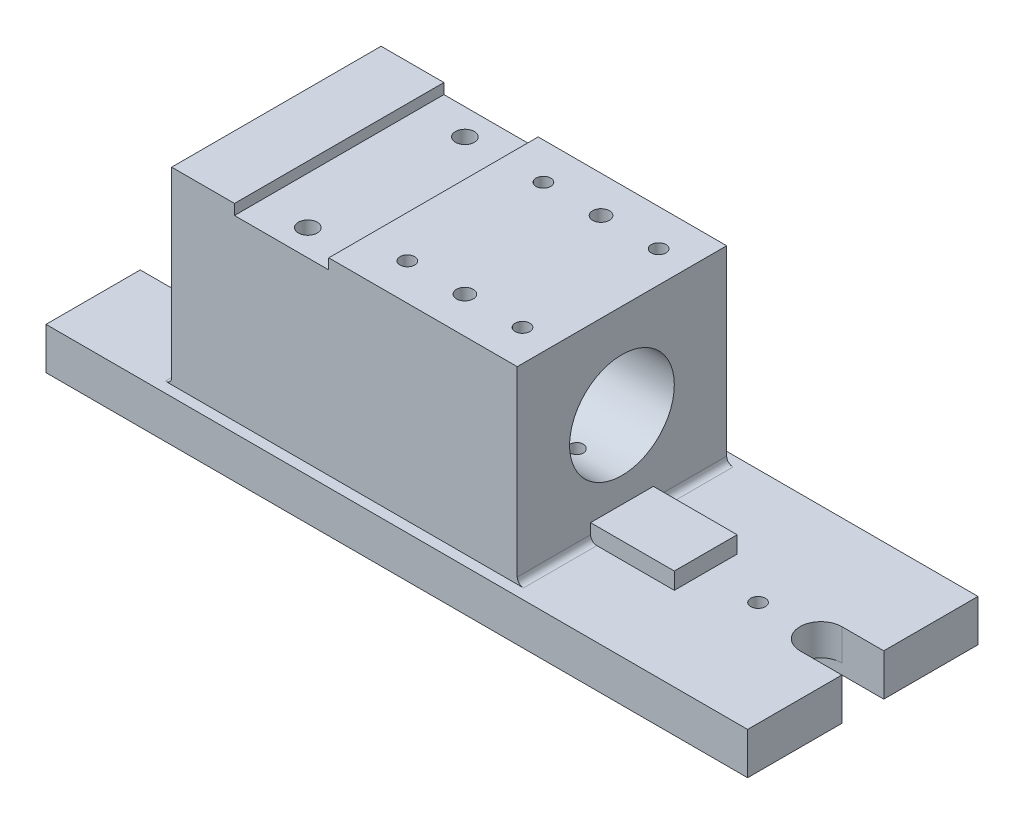
SolidWorks part; units mm, degrees
ref_plane "Спереди" through (0, 0, 0) normal (0, 0, 1) x (1, 0, 0)
ref_plane "Сверху" through (0, 0, 0) normal (0, 1, 0) x (1, 0, 0)
ref_plane "Справа" through (0, 0, 0) normal (1, 0, 0) x (0, 0, -1)
sketch "Эскиз1" plane through (0, 0, 0) normal (0, 1, 0) x (1, 0, 0)
  line L0 (-1085.7045, 0) -> (53199.5194, 0) construction
  line L1 (0, -1085.7045) -> (0, 53199.5194) construction
  line L2 (-147.5, 10) -> (-167.5, 10)
  line L3 (-167.5, -55) -> (167.5, -55)
  line L4 (-167.5, -55) -> (-167.5, -10)
  line L5 (-167.5, 55) -> (167.5, 55)
  line L6 (167.5, -55) -> (167.5, -10)
  line L7 (-167.5, -55) -> (167.5, 55) construction
  line L8 (-167.5, 55) -> (167.5, -55) construction
  line L9 (-147.5, -10) -> (-167.5, -10)
  line L10 (147.5, 10) -> (167.5, 10)
  line L11 (147.5, -10) -> (167.5, -10)
  line L12 (167.5, 10) -> (167.5, 55)
  line L13 (-167.5, 10) -> (-167.5, 55)
  arc A0 (-147.5, -10) -> (-147.5, 10) centre (-147.5, 0) ccw
  arc A1 (147.5, 10) -> (147.5, -10) centre (147.5, 0) ccw
  point P4 (0, 0)
  dimension "D3" = 20
  dimension "D1" = 335
  dimension "D2" = 110
  dimension "D4" = 20
  dimension "D5" = 20
extrude "Бобышка-Вытянуть1" add sketch "Эскиз1" along normal blind 20
sketch "Эскиз2" plane through (0, 0, 0) normal (0, -1, 0) x (1, 0, 0)
  line L0 (-1000, 0) -> (49000, 0) construction
  line L1 (167.5, 55) -> (167.5, 10) construction
  line L2 (40.5, -35) -> (-95.5, -35)
  line L3 (42.5, -33) -> (42.5, 33)
  line L4 (40.5, 35) -> (-95.5, 35)
  line L5 (-97.5, -33) -> (-97.5, 33)
  line L6 (42.5, -35) -> (-97.5, 35) construction
  line L7 (42.5, 35) -> (-97.5, -35) construction
  arc A0 (-95.5, -35) -> (-97.5, -33) centre (-95.5, -33) cw
  arc A1 (40.5, -35) -> (42.5, -33) centre (40.5, -33) ccw
  arc A2 (42.5, 33) -> (40.5, 35) centre (40.5, 33) ccw
  arc A3 (-95.5, 35) -> (-97.5, 33) centre (-95.5, 33) ccw
  point P1 (-27.5, 0)
  dimension "D4" = 2
  dimension "D1" = 70
  dimension "D2" = 125
  dimension "D3" = 265
extrude "Вырез-Вытянуть1" cut sketch "Эскиз2" against normal blind 16
sketch "Эскиз3" plane through (-167.5, 0, 0) normal (-1, 0, 0) x (0, 0, 1)
  line L0 (-10, 20) -> (-10, 0) construction
  line L1 (-10, 5) -> (10, 5)
  line L2 (-10, 5) -> (-10, 0)
  line L3 (-10, 0) -> (10, 0)
  line L4 (10, 5) -> (10, 0)
  line L5 (10, 20) -> (10, 0) construction
  line L6 (-55, 0) -> (-10, 0) construction
  dimension "D1" = 5
extrude "Вырез-Вытянуть2" cut sketch "Эскиз3" against normal through all
sketch "Эскиз4" plane through (0, 20, 0) normal (0, 1, 0) x (1, 0, 0)
  line L0 (-1000, 0) -> (49000, 0) construction
  line L1 (167.5, 10) -> (167.5, 55) construction
  line L2 (-112.5, -50) -> (52.5, -50)
  line L3 (-112.5, -50) -> (-112.5, 50)
  line L4 (-112.5, 50) -> (52.5, 50)
  line L5 (52.5, -50) -> (52.5, 50)
  line L6 (-112.5, -50) -> (52.5, 50) construction
  line L7 (-112.5, 50) -> (52.5, -50) construction
  point P1 (-30, 0)
  dimension "D1" = 100
  dimension "D2" = 115
  dimension "D3" = 280
extrude "Бобышка-Вытянуть2" add sketch "Эскиз4" along normal blind 90
sketch "Эскиз5" plane through (0, 0, 50) normal (0, 0, 1) x (1, 0, 0)
  line L0 (-112.5, 110) -> (52.5, 110) construction
  line L1 (-82.5, 110) -> (-37.5, 110)
  line L2 (-82.5, 110) -> (-82.5, 105)
  line L3 (-82.5, 105) -> (-37.5, 105)
  line L4 (-37.5, 110) -> (-37.5, 105)
  line L5 (167.5, 20) -> (167.5, 0) construction
  dimension "D1" = 5
  dimension "D2" = 205
  dimension "D3" = 250
extrude "Вырез-Вытянуть3" cut sketch "Эскиз5" against normal up to next
sketch "Эскиз6" plane through (0, 20, 0) normal (0, 1, 0) x (1, 0, 0)
  line L0 (-1000, 0) -> (49000, 0) construction
  line L1 (52.5, -50) -> (52.5, 50) construction
  line L2 (92.5, -15) -> (52.5, -15)
  line L3 (92.5, -15) -> (92.5, 15)
  line L4 (92.5, 15) -> (52.5, 15)
  line L5 (52.5, -15) -> (52.5, 15)
  line L6 (92.5, -15) -> (52.5, 15) construction
  line L7 (92.5, 15) -> (52.5, -15) construction
  line L8 (167.5, 10) -> (167.5, 55) construction
  point P1 (72.5, 0)
  dimension "D1" = 30
  dimension "D2" = 75
extrude "Бобышка-Вытянуть3" add sketch "Эскиз6" along normal blind 8
sketch "Эскиз7" plane through (-167.5, 0, 0) normal (-1, 0, 0) x (0, 0, 1)
  line L1 (0, 0) -> (91.7061, 0)
  line L2 (0, 0) -> (0, 136.0495)
  line L3 (0, 136.0495) -> (91.7061, 136.0495)
  line L4 (91.7061, 0) -> (91.7061, 136.0495)
  dimension "D1" = 91.7061
  dimension "D2" = 136.0495
extrude "Вырез-Вытянуть4" cut sketch "Эскиз7" against normal through all
sketch "Эскиз8" plane through (0, 0, 0) normal (0, 0, 1) x (1, 0, 0)
  line L0 (-112.5, 65) -> (52.5, 65)
  line L1 (-112.5, 20) -> (-112.5, 110) construction
  line L2 (52.5, 110) -> (52.5, 28) construction
  line L3 (-112.5, 65) -> (-112.5, 37)
  line L4 (-112.5, 37) -> (-77.5, 37)
  line L5 (-77.5, 37) -> (-77.5, 35)
  line L6 (-77.5, 35) -> (-72.5, 35)
  line L7 (-72.5, 35) -> (-72.5, 50)
  line L8 (-72.5, 50) -> (-68.0718, 50)
  line L9 (-68.0718, 50) -> (-67, 46)
  line L10 (-67, 46) -> (-63, 46)
  line L11 (-63, 46) -> (-61.9282, 50)
  line L12 (-61.9282, 50) -> (-58.0785, 50)
  line L13 (-58.0785, 50) -> (-57, 45.9751)
  line L14 (-57, 45.9751) -> (-53, 45.9751)
  line L15 (-53, 45.9751) -> (-51.9215, 50)
  line L16 (-51.9215, 50) -> (-47.5, 50)
  line L17 (-47.5, 50) -> (-47.5, 40)
  line L18 (-47.5, 40) -> (52.5, 40)
  line L19 (52.5, 40) -> (52.5, 65)
  line L20 (-1102.5277, 65) -> (48897.4723, 65) construction
  dimension "D1" = 65
  dimension "D2" = 35
  dimension "D3" = 40
  dimension "D4" = 28
  dimension "D5" = 30
  dimension "D6" = 15
  dimension "D7" = 19
  dimension "D8" = 5.5
  dimension "D9" = 9.5
  dimension "D10" = 15.5
  dimension "D11" = 19.5
  dimension "D12" = 100
  dimension "D13" = 105
  dimension "D14" = 105
  dimension "D15" = 4.1669
  dimension "D16" = 25
revolve "Вырез-Повернуть1" cut sketch "Эскиз8" angle 360 about L20
mirror "Зеркальное отражение1" about plane through (167.5, 0, 0) normal (0, 0, -1) of "Бобышка-Вытянуть1", "Вырез-Вытянуть2", "Вырез-Вытянуть1", "Бобышка-Вытянуть2", "Вырез-Вытянуть3", "Бобышка-Вытянуть3", "Вырез-Повернуть1"
sketch "Эскиз9" plane through (0, 16, 0) normal (0, -1, 0) x (1, 0, 0)
  line L0 (-1000, 0) -> (49000, 0) construction
  line L1 (167.5, 10) -> (167.5, 55) construction
  circle A0 centre (30.5, 0) radius 7
  dimension "D1" = 14
  dimension "D2" = 137
extrude "Вырез-Вытянуть5" cut sketch "Эскиз9" against normal blind 5
hole_wizard "Сверление под метчик M8x1.01" positions "Трехмерный эскиз1" profile "Эскиз10" hole size "M8x1.0" standard "Ansi Metric" end condition up to next
sketch3d "Трехмерный эскиз1"
  line L0 (30.5, 21, 0) -> (30.5, 16, 0) construction
  point P0 (30.5, 16, 0)
sketch "Эскиз10" plane through (30.5, 16, 0) normal (1, 0, 0) x (0, 0, -1)
  line L0 (0, 0) -> (0, 24)
  line L1 (0, 24) -> (3.5, 24)
  line L2 (3.5, 24) -> (3.5, 0)
  line L5 (3.5, 0) -> (0, 0)
  line L11 (0, -6.35) -> (0, 107.95) construction
  dimension "Диаметр сквозного отверстия" = 7
  dimension "Глубина сквозного отверстия" = 24
cosmetic thread "Условное изображение резьбы1" parameters "D2"=8
sketch "Эскиз12" plane through (0, 20, 0) normal (0, 1, 0) x (1, 0, 0)
  line L0 (-1000, 0) -> (49000, 0) construction
  line L1 (167.5, -10) -> (167.5, -55) construction
  point P1 (117.5, 0)
  point P4 (-122.5, 0)
  dimension "D1" = 290
  dimension "D2" = 50
hole_wizard "Сверление под метчик M8x1.02" positions "Трехмерный эскиз3" profile "Эскиз13" hole size "M8x1.0" standard "Ansi Metric" end condition up to next
sketch3d "Трехмерный эскиз3"
  point P0 (-122.5, 20, 0)
  point P3 (117.5, 20, 0)
sketch "Эскиз13" plane through (-122.5, 20, 0) normal (1, 0, 0) x (0, 0, 1)
  line L0 (0, 0) -> (0, 15)
  line L1 (0, 15) -> (3.5, 15)
  line L2 (3.5, 15) -> (3.5, 0)
  line L5 (3.5, 0) -> (0, 0)
  line L11 (0, -6.35) -> (0, 107.95) construction
  dimension "Диаметр сквозного отверстия" = 7
  dimension "Глубина сквозного отверстия" = 15
cosmetic thread "Условное изображение резьбы2" parameters "D2"=8
cosmetic thread "Условное изображение резьбы3" parameters "D2"=8
sketch "Эскиз14" plane through (0, 110, 0) normal (0, 1, 0) x (1, 0, 0)
  line L0 (-1000, 0) -> (49000, 0) construction
  line L1 (167.5, -10) -> (167.5, -55) construction
  line L2 (37.5, -32.5) -> (-17.5, -32.5) construction
  line L3 (37.5, -32.5) -> (37.5, 32.5) construction
  line L4 (37.5, 32.5) -> (-17.5, 32.5) construction
  line L5 (-17.5, -32.5) -> (-17.5, 32.5) construction
  line L6 (37.5, -32.5) -> (-17.5, 32.5) construction
  line L7 (37.5, 32.5) -> (-17.5, -32.5) construction
  line L8 (10, -32.5) -> (10, 32.5) construction
  point P1 (10, 0)
  point P8 (167.5, -32.5)
  point P14 (-17.5, 32.5)
  point P15 (10, 32.5)
  point P16 (37.5, 32.5)
  point P17 (37.5, -32.5)
  point P18 (10, -32.5)
  point P19 (-17.5, -32.5)
  dimension "D1" = 65
  dimension "D2" = 130
  dimension "D3" = 185
  dimension "D4" = 157.5
hole_wizard "Сверление под метчик M8x1.03" positions "Трехмерный эскиз4" profile "Эскиз16" hole size "M8x1.0" standard "Ansi Metric"
sketch3d "Трехмерный эскиз4"
  point P0 (-17.5, 110, -32.5)
  point P3 (37.5, 110, -32.5)
  point P6 (37.5, 110, 32.5)
  point P9 (-17.5, 110, 32.5)
sketch "Эскиз16" plane through (-17.5, 110, -32.5) normal (1, 0, 0) x (0, 0, 1)
  line L0 (0, 0) -> (0, 25.103)
  line L1 (0, 25.103) -> (3.5, 23)
  line L2 (3.5, 23) -> (3.5, 0)
  line L5 (3.5, 0) -> (0, 0)
  line L10 (0, 25.103) -> (-3.5, 23) construction
  line L11 (0, -6.35) -> (0, 107.95) construction
  dimension "Диаметр отверстия" = 7
  dimension "Глубина отверстия" = 23
  dimension "Угол заточки сверла" = 118
cosmetic thread "Условное изображение резьбы4" parameters "D1"=20, "D2"=8
cosmetic thread "Условное изображение резьбы5" parameters "D1"=20, "D2"=8
cosmetic thread "Условное изображение резьбы6" parameters "D1"=20, "D2"=8
cosmetic thread "Условное изображение резьбы7" parameters "D1"=20, "D2"=8
hole_wizard "Диаметр отверстия Ø9.0 (9)1" positions "Трехмерный эскиз5" profile "Эскиз17" hole size "Ø9.0" standard "Ansi Metric"
sketch3d "Трехмерный эскиз5"
  point P0 (10, 110, -32.5)
  point P3 (10, 110, 32.5)
sketch "Эскиз17" plane through (10, 110, -32.5) normal (1, 0, 0) x (0, 0, 1)
  line L0 (0, 0) -> (0, 17.4034)
  line L1 (0, 17.4034) -> (4, 15)
  line L2 (4, 15) -> (4, 0)
  line L5 (4, 0) -> (0, 0)
  line L10 (0, 17.4034) -> (-4, 15) construction
  line L11 (0, -6.35) -> (0, 107.95) construction
  dimension "Диаметр отверстия" = 8
  dimension "Глубина отверстия" = 15
  dimension "Угол заточки сверла" = 118
sketch "Эскиз18" plane through (0, 105, 0) normal (0, 1, 0) x (1, 0, 0)
  line L0 (-1000, 0) -> (49000, 0) construction
  line L1 (-60, 37.5) -> (-60, -37.5) construction
  line L2 (167.5, -10) -> (167.5, -55) construction
  line L3 (-82.5, -50) -> (-37.5, -50) construction
  line L5 (-82.5, 50) -> (-37.5, 50) construction
  point P8 (-60, 37.5)
  point P9 (-60, -37.5)
  dimension "D1" = 12.5
  dimension "D3" = 227.5
  dimension "D4" = 12.5
hole_wizard "Сверление под метчик M10x1.02" positions "Трехмерный эскиз6" profile "Эскиз19" hole size "M10x1.0" standard "Ansi Metric"
sketch3d "Трехмерный эскиз6"
  point P0 (-60, 105, -37.5)
  point P3 (-60, 105, 37.5)
sketch "Эскиз19" plane through (-60, 105, -37.5) normal (1, 0, 0) x (0, 0, 1)
  line L0 (0, 0) -> (0, 24.7039)
  line L1 (0, 24.7039) -> (4.5, 22)
  line L2 (4.5, 22) -> (4.5, 0)
  line L5 (4.5, 0) -> (0, 0)
  line L10 (0, 24.7039) -> (-4.5, 22) construction
  line L11 (0, -6.35) -> (0, 107.95) construction
  dimension "Диаметр отверстия" = 9
  dimension "Глубина отверстия" = 22
  dimension "Угол заточки сверла" = 118
cosmetic thread "Условное изображение резьбы9" parameters "D1"=18, "D2"=10
cosmetic thread "Условное изображение резьбы10" parameters "D1"=18, "D2"=10
sketch "Эскиз20" plane through (0, 0, -50) normal (0, 0, -1) x (-1, 0, 0)
  line L0 (-978.1938, 65) -> (49021.8062, 65) construction
  line L1 (-167.5, 0) -> (167.5, 0) construction
  line L2 (-167.5, 20) -> (-167.5, 0) construction
  point P4 (84.5, 65)
  dimension "D1" = 65
  dimension "D2" = 252
sketch "Эскиз22" plane through (-112.5, 0, 0) normal (-1, 0, 0) x (0, 0, 1)
  line L0 (0, -935) -> (0, 49065) construction
  circle A0 centre (0, 65) radius 35 construction
  point P3 (0, 100)
  point P6 (33.287, 75.8156)
  point P9 (20.5725, 36.6844)
  point P10 (-20.5725, 36.6844)
  point P11 (-33.287, 75.8156)
  point P12 (0, 65)
  dimension "D1" = 70
  dimension "D2" = 5
hole_wizard "Сверление под метчик M6x1.01" positions "Трехмерный эскиз8" profile "Эскиз23" hole size "M6x1.0" standard "Ansi Metric"
sketch3d "Трехмерный эскиз8"
  point P0 (-112.5, 75.8156, -33.287)
  point P3 (-112.5, 100, 0)
  point P6 (-112.5, 75.8156, 33.287)
  point P9 (-112.5, 36.6844, 20.5725)
  point P12 (-112.5, 36.6844, -20.5725)
sketch "Эскиз23" plane through (-112.5, 75.8156, -33.287) normal (0, 1, 0) x (0, 0, 1)
  line L0 (0, 0) -> (0, 13.5022)
  line L1 (0, 13.5022) -> (2.5, 12)
  line L2 (2.5, 12) -> (2.5, 0)
  line L5 (2.5, 0) -> (0, 0)
  line L10 (0, 13.5022) -> (-2.5, 12) construction
  line L11 (0, -6.35) -> (0, 107.95) construction
  dimension "Диаметр отверстия" = 5
  dimension "Глубина отверстия" = 12
  dimension "Угол заточки сверла" = 118
cosmetic thread "Условное изображение резьбы11" parameters "D1"=10, "D2"=6
cosmetic thread "Условное изображение резьбы12" parameters "D1"=10, "D2"=6
cosmetic thread "Условное изображение резьбы13" parameters "D1"=10, "D2"=6
cosmetic thread "Условное изображение резьбы14" parameters "D1"=10, "D2"=6
cosmetic thread "Условное изображение резьбы15" parameters "D1"=10, "D2"=6
fillet "Скругление1" radius 3 3 edges at (52.5, 20, -32.5) (52.5, 20, 32.5) (-112.5, 20, 0)
fillet "Скругление4" radius 3 8 edges at (-96.9142, 16, -34.4142) (-27.5, 16, -35) (41.9142, 16, -34.4142) (41.9142, 16, 34.4142) (-27.5, 16, 35) (-96.9142, 16, 34.4142) (42.5, 16, 0) (-97.5, 16, 0)
sketch "Эскиз25" plane through (0, 110, 0) normal (0, 1, 0) x (1, 0, 0)
